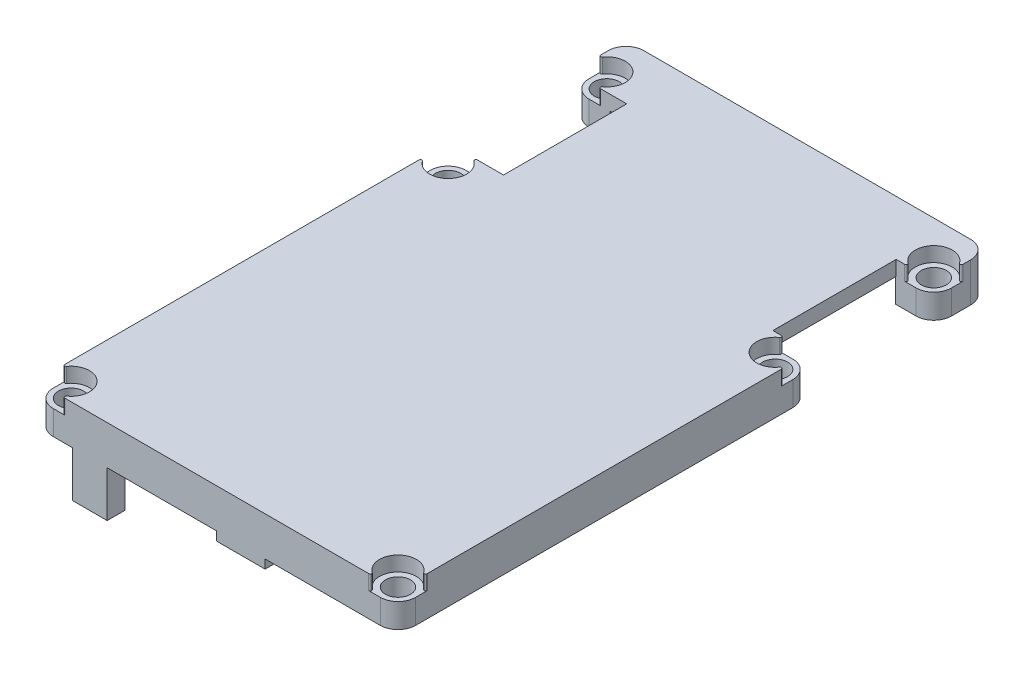
SolidWorks part; units mm, degrees
ref_plane "Front Plane" through (0, 0, 0) normal (0, 0, 1) x (1, 0, 0)
ref_plane "Top Plane" through (0, 0, 0) normal (0, 1, 0) x (1, 0, 0)
ref_plane "Right Plane" through (0, 0, 0) normal (1, 0, 0) x (0, 0, -1)
sketch "Sketch1" plane through (0, 0, 0) normal (0, 1, 0) x (1, 0, 0)
  line L1 (0, 0) -> (49.1, 0)
  line L2 (0, 0) -> (0, -80)
  line L3 (0, -80) -> (49.1, -80)
  line L4 (49.1, 0) -> (49.1, -80)
  dimension "D1" = 80
  dimension "D2" = 49.1
extrude "Boss-Extrude1" add sketch "Sketch1" along normal blind 2
sketch "Sketch2" plane through (0, 2, 0) normal (0, 1, 0) x (1, 0, 0)
  line L0 (49.1, 0) -> (0, 0) construction
  line L1 (2.4, -5) -> (46.7, -5) construction
  line L2 (2.4, -5) -> (2.4, -26.5) construction
  line L3 (2.4, -26.5) -> (46.7, -26.5) construction
  line L4 (46.7, -5) -> (46.7, -26.5) construction
  line L5 (0, 0) -> (0, -80) construction
  line L6 (24.55, -5) -> (24.55, 0) construction
  line L7 (0, -80) -> (49.1, -80) construction
  line L8 (24.55, -80) -> (24.55, -37.9836) construction
  circle A0 centre (2.4, -77.6) radius 1.7
  circle A1 centre (2.4, -26.5) radius 1.7
  circle A2 centre (2.4, -5) radius 1.7
  circle A3 centre (46.7, -77.6) radius 1.7
  circle A4 centre (46.7, -26.5) radius 1.7
  circle A5 centre (46.7, -5) radius 1.7
  dimension "D5" = 3.4
  dimension "D6" = 2.4
  dimension "D7" = 2.4
  dimension "D1" = 5
  dimension "D2" = 21.5
  dimension "D3" = 44.3
extrude "Cut-Extrude1" cut sketch "Sketch2" against normal blind 2
sketch "Sketch3" plane through (0, 0, 0) normal (0, -1, 0) x (1, 0, 0)
  line L0 (24.55, 80) -> (24.55, 0) construction
  line L1 (0, 80) -> (5.2, 80)
  line L2 (0, 80) -> (0, 74.8)
  line L3 (0, 74.8) -> (5.2, 74.8)
  line L4 (5.2, 80) -> (5.2, 74.8)
  line L5 (0, 80) -> (49.1, 80) construction
  line L6 (49.1, 0) -> (0, 0) construction
  line L7 (2.4, 26.5) -> (2.4, 5) construction
  line L8 (2.4, 15.75) -> (24.55, 15.75) construction
  line L9 (0, 0) -> (0, 80) construction
  line L10 (5.2, 29.3) -> (0, 29.3)
  line L11 (5.2, 29.3) -> (5.2, 24.1)
  line L12 (5.2, 24.1) -> (0, 24.1)
  line L13 (0, 29.3) -> (0, 24.1)
  line L16 (5.2, 7.4) -> (0, 2.2) construction
  line L17 (5.2, 2.2) -> (0, 7.4) construction
  line L18 (0, 2.2) -> (0, 7.4)
  line L19 (5.2, 7.4) -> (0, 7.4)
  line L20 (5.2, 2.2) -> (5.2, 7.4)
  line L21 (5.2, 2.2) -> (0, 2.2)
  line L22 (43.9, 2.2) -> (49.1, 7.4) construction
  line L23 (43.9, 7.4) -> (49.1, 2.2) construction
  line L24 (43.9, 24.1) -> (49.1, 29.3) construction
  line L25 (43.9, 29.3) -> (49.1, 24.1) construction
  line L26 (46.7, 26.5) -> (46.7, 5) construction
  line L27 (43.9, 2.2) -> (49.1, 2.2)
  line L28 (43.9, 2.2) -> (43.9, 7.4)
  line L29 (43.9, 7.4) -> (49.1, 7.4)
  line L30 (49.1, 2.2) -> (49.1, 7.4)
  line L31 (49.1, 29.3) -> (49.1, 24.1)
  line L32 (43.9, 24.1) -> (49.1, 24.1)
  line L33 (43.9, 29.3) -> (43.9, 24.1)
  line L34 (43.9, 29.3) -> (49.1, 29.3)
  line L35 (43.9, 80) -> (43.9, 74.8)
  line L36 (49.1, 74.8) -> (43.9, 74.8)
  line L37 (49.1, 80) -> (49.1, 74.8)
  line L38 (49.1, 80) -> (43.9, 80)
  circle A0 centre (2.4, 77.6) radius 1.7
  circle A1 centre (2.4, 77.6) radius 1.7 construction
  circle A2 centre (2.4, 26.5) radius 1.7
  circle A3 centre (2.4, 26.5) radius 1.7 construction
  circle A4 centre (2.4, 5) radius 1.7
  circle A5 centre (46.7, 5) radius 1.7
  circle A6 centre (46.7, 26.5) radius 1.7
  circle A7 centre (46.7, 77.6) radius 1.7
  dimension "D1" = 5.2
  dimension "D2" = 2.4
  dimension "D3" = 2.8
  dimension "D4" = 5.2
  dimension "D5" = 5.2
extrude "Boss-Extrude2" add sketch "Sketch3" along normal blind 3.3
sketch "Sketch4" plane through (0, 2, 0) normal (0, 1, 0) x (1, 0, 0)
  line L0 (0, 0) -> (0, -80) construction
  line L1 (0, -7.4) -> (7.5, -7.4)
  line L2 (0, -7.4) -> (0, -24.1)
  line L3 (0, -24.1) -> (7.5, -24.1)
  line L4 (7.5, -7.4) -> (7.5, -24.1)
  line L5 (2.4, -5) -> (2.4, -26.5) construction
  line L6 (2.4, -15.75) -> (7.5, -15.75) construction
  line L7 (49.1, -80) -> (49.1, 0) construction
  line L8 (49.1, -7.4) -> (44, -7.4)
  line L9 (49.1, -7.4) -> (49.1, -24.1)
  line L10 (49.1, -24.1) -> (44, -24.1)
  line L11 (44, -7.4) -> (44, -24.1)
  line L12 (44, -15.75) -> (7.5, -15.75) construction
  line L13 (5.2, -7.4) -> (0, -7.4) construction
  line M13 (0, 0) -> (0, -80)
  line M15 (49.1, -80) -> (49.1, 0)
  dimension "D1" = 7.5
  dimension "D4" = 5.1
extrude "Cut-Extrude2" cut sketch "Sketch4" against normal blind 3.3 contours L4 L1 L3 M13 | L8 L11 L10 M15 region at (3.75, 2, 15.75) region at (46.55, 2, 15.75)
sketch "Sketch6" plane through (0, 0, 0) normal (0, -1, 0) x (1, 0, 0)
  line L0 (49.1, 46.0108) -> (0, 46.0108) construction
  line L5 (11.8806, 53.3353) -> (37.2194, 53.3353)
  line L6 (11.8806, 53.3353) -> (11.8806, 38.6862)
  line L7 (11.8806, 38.6862) -> (37.2194, 38.6862)
  line L8 (37.2194, 53.3353) -> (37.2194, 38.6862)
  line L9 (11.8806, 53.3353) -> (37.2194, 38.6862) construction
  line L10 (11.8806, 38.6862) -> (37.2194, 53.3353) construction
  line L11 (49.1, 74.8) -> (49.1, 29.3) construction
  line L12 (0, 29.3) -> (0, 74.8) construction
  line L13 (24.55, 80) -> (24.55, 12.0215) construction
  line L14 (5.2, 80) -> (43.9, 80) construction
  point P4 (24.55, 46.0108)
extrude "Boss-Extrude3" [suppressed] add sketch "Sketch6" along normal blind 3.2
sketch "Sketch7" plane through (0, 0, 0) normal (0, -1, 0) x (1, 0, 0)
  line L1 (5.2, 80) -> (43.9, 80)
  line L2 (5.2, 80) -> (5.2, 77.6)
  line L3 (5.2, 77.6) -> (43.9, 77.6)
  line L4 (43.9, 80) -> (43.9, 77.6)
  line L6 (46.7, 74.8) -> (49.1, 74.8)
  line L7 (46.7, 74.8) -> (46.7, 29.3)
  line L8 (46.7, 29.3) -> (49.1, 29.3)
  line L9 (49.1, 74.8) -> (49.1, 29.3)
  line L11 (2.4, 74.8) -> (0, 74.8)
  line L12 (2.4, 74.8) -> (2.4, 29.3)
  line L13 (2.4, 29.3) -> (0, 29.3)
  line L14 (0, 74.8) -> (0, 29.3)
  line L15 (49.1, 2.2) -> (49.1, 0) construction
  line L16 (0, 0) -> (49.1, 0)
  line L17 (0, 0) -> (0, 2)
  line L18 (5.2, 2) -> (43.9, 2)
  line L19 (49.1, 0) -> (49.1, 2)
  line L20 (5.2, 2.2) -> (5.2, 7.4) construction
  line L21 (0, 2.2) -> (5.2, 2.2)
  line L22 (0, 2.2) -> (0, 2)
  line L24 (5.2, 2.2) -> (5.2, 2)
  line L25 (0, 2.2) -> (5.2, 2.2) construction
  line L26 (0, 74.8) -> (5.2, 74.8) construction
  line L28 (49.1, 2) -> (49.1, 2.2)
  line L29 (49.1, 2.2) -> (43.9, 2.2)
  line L30 (43.9, 2) -> (43.9, 2.2)
  line L31 (43.9, 74.8) -> (49.1, 74.8) construction
  dimension "D1" = 2
  dimension "D2" = 2
  dimension "D3" = 2.4
  dimension "D4" = 2.4
  dimension "D5" = 2.4
extrude "Boss-Extrude4" add sketch "Sketch7" along normal up to surface (3.3 mm away) up to face at (46.5, -3.3, 26.7)
sketch "Sketch8" plane through (0, 0, 80) normal (0, 0, 1) x (1, 0, 0)
  line L0 (49.1, -3.3) -> (0, -3.3) construction
  line L1 (24.5, -3.3) -> (31.1, -3.3)
  line L2 (24.5, -3.3) -> (24.5, -4.5)
  line L3 (24.5, -4.5) -> (31.1, -4.5)
  line L4 (31.1, -3.3) -> (31.1, -4.5)
  line L6 (27.8, -4.5) -> (27.8, 0) construction
  line L7 (49.1, 2) -> (49.1, -3.3) construction
  line L8 (5, -3.3) -> (9.7, -3.3)
  line L9 (5, -3.3) -> (5, -9.5)
  line L10 (5, -9.5) -> (9.7, -9.5)
  line L11 (9.7, -3.3) -> (9.7, -9.5)
  line L12 (7.35, -9.5) -> (7.35, 5.3073) construction
  line L13 (0, 2) -> (0, -3.3) construction
  dimension "D1" = 1.2
  dimension "D2" = 6.6
  dimension "D3" = 21.3
  dimension "D4" = 6.2
  dimension "D5" = 7.35
  dimension "D6" = 4.7
extrude "Boss-Extrude5" add sketch "Sketch8" against normal up to surface (2.4 mm away) up to face at (24.55, -1.65, 77.6)
fillet "Fillet1" radius 2.4 8 edges at (0, -0.65, 80) (49.1, -0.65, 80) (49.1, -0.65, 24.1) (49.1, -0.65, 7.4) (0, -0.65, 7.4) (0, -0.65, 24.1) (0, -0.65, 0) (49.1, -0.65, 0)
sketch "Sketch9" plane through (0, 2, 0) normal (0, 1, 0) x (1, 0, 0)
  line L0 (24.55, 0) -> (24.55, -80) construction
  line L1 (46.7, 0) -> (2.4, 0) construction
  line L2 (2.4, -80) -> (46.7, -80) construction
  circle A0 centre (2.4, -5) radius 2.5
  circle A1 centre (2.4, -26.5) radius 2.5
  circle A2 centre (2.4, -77.6) radius 2.5
  circle A3 centre (46.7, -77.6) radius 2.5
  circle A4 centre (46.7, -26.5) radius 2.5
  circle A5 centre (46.7, -5) radius 2.5
  dimension "D1" = 5
extrude "Cut-Extrude3" cut sketch "Sketch9" against normal blind 2
fillet "Fillet2" radius 0.2 12 edges at (46, 1, 7.4) (46, 1, 24.1) (49.1, 1, 27.2) (46, 1, 80) (0, 1, 27.2) (3.1, 1, 24.1) (3.1, 1, 7.4) (0, 1, 4.3) (49.1, 1, 4.3) (49.1, 1, 76.9) (3.1, 1, 80) (0, 1, 76.9)
